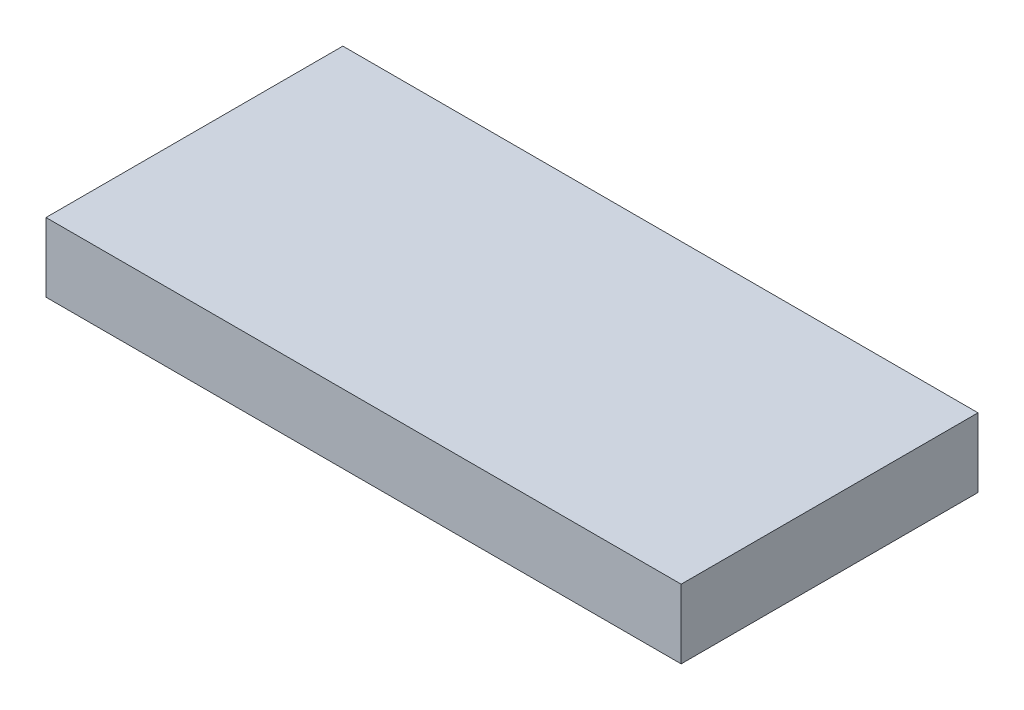
SolidWorks part; units mm, degrees
ref_plane "Front Plane" through (0, 0, 0) normal (0, 0, 1) x (1, 0, 0)
ref_plane "Top Plane" through (0, 0, 0) normal (0, 1, 0) x (1, 0, 0)
ref_plane "Right Plane" through (0, 0, 0) normal (1, 0, 0) x (0, 0, -1)
sketch "Sketch1" plane through (0, 0, 0) normal (0, 1, 0) x (1, 0, 0)
  line L1 (92, 43) -> (-92, 43)
  line L2 (92, 43) -> (92, -43)
  line L3 (92, -43) -> (-92, -43)
  line L4 (-92, 43) -> (-92, -43)
  line L5 (92, 43) -> (-92, -43) construction
  line L6 (92, -43) -> (-92, 43) construction
  point P0 (0, 0)
  dimension "D1" = 184
  dimension "D2" = 86
extrude "plate" add sketch "Sketch1" along normal blind 20
equation "\"D1@Sketch1\"=144+40"
equation "\"D2@Sketch1\"=46+40"
